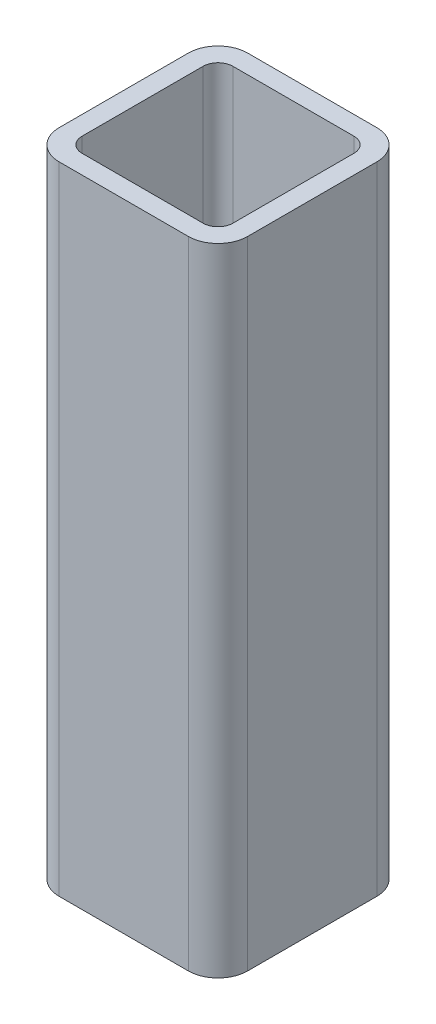
SolidWorks part; units mm, degrees
ref_plane "Front Plane" through (0, 0, 0) normal (0, 0, 1) x (1, 0, 0)
ref_plane "Top Plane" through (0, 0, 0) normal (0, 1, 0) x (1, 0, 0)
ref_plane "Right Plane" through (0, 0, 0) normal (1, 0, 0) x (0, 0, -1)
sketch "Sketch1" plane through (0, 0, 0) normal (0, 1, 0) x (1, 0, 0)
  line L1 (4, 0) -> (21.4, 0)
  line L2 (0, 4) -> (0, 21.4)
  line L3 (4, 25.4) -> (21.4, 25.4)
  line L4 (25.4, 4) -> (25.4, 21.4)
  line L6 (20.86, 2.54) -> (4.54, 2.54)
  line L7 (22.86, 4.54) -> (22.86, 20.86)
  line L8 (2.54, 4.54) -> (2.54, 20.86)
  line L9 (20.86, 22.86) -> (4.54, 22.86)
  line L10 (22.86, 2.54) -> (2.54, 22.86) construction
  line L11 (2.54, 2.54) -> (22.86, 22.86) construction
  arc A0 (2.54, 20.86) -> (4.54, 22.86) centre (4.54, 20.86) cw
  arc A1 (22.86, 20.86) -> (20.86, 22.86) centre (20.86, 20.86) ccw
  arc A2 (22.86, 4.54) -> (20.86, 2.54) centre (20.86, 4.54) cw
  arc A3 (4.54, 2.54) -> (2.54, 4.54) centre (4.54, 4.54) cw
  arc A4 (0, 21.4) -> (4, 25.4) centre (4, 21.4) cw
  arc A5 (21.4, 25.4) -> (25.4, 21.4) centre (21.4, 21.4) cw
  arc A6 (21.4, 0) -> (25.4, 4) centre (21.4, 4) ccw
  arc A7 (4, 0) -> (0, 4) centre (4, 4) cw
  point P9 (12.7, 12.7)
  point P31 (0, 0)
  dimension "D1" = 2
  dimension "D2" = 2
  dimension "D3" = 4
  dimension "D4" = 4
  dimension "D5" = 4
  dimension "D6" = 4
extrude "Boss-Extrude1" add sketch "Sketch1" along normal up to surface (85.725 mm away)
